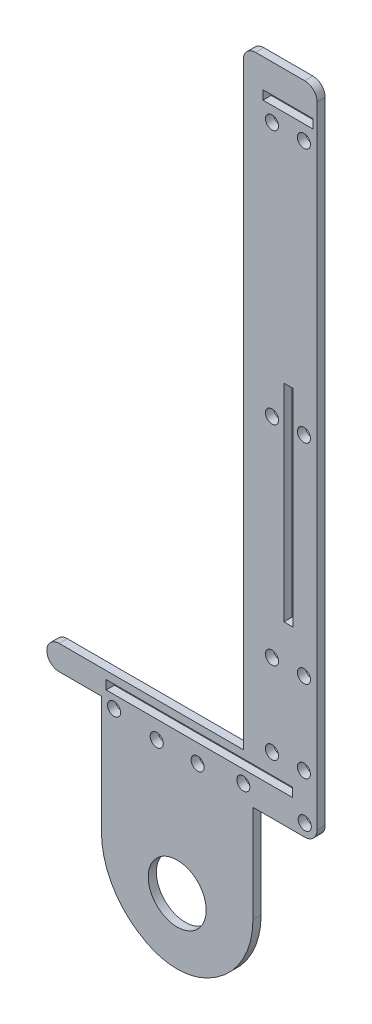
SolidWorks part; units mm, degrees
ref_plane "前视基准面" through (0, 0, 0) normal (0, 0, 1) x (1, 0, 0)
ref_plane "上视基准面" through (0, 0, 0) normal (0, 1, 0) x (1, 0, 0)
ref_plane "右视基准面" through (0, 0, 0) normal (1, 0, 0) x (0, 0, -1)
sketch "草图1" plane through (0, 0, 0) normal (0, 0, 1) x (1, 0, 0)
  line L0 (-45.6533, -106) -> (-45.6533, -80.5)
  line L1 (-11, -74.5) -> (11, -74.5)
  line L2 (-11, -74.5) -> (-11, 74.5)
  line L3 (-11, 74.5) -> (11, 74.5)
  line L4 (11, -74.5) -> (11, 74.5)
  line L5 (-11, -74.5) -> (11, 74.5) construction
  line L6 (-11, 74.5) -> (11, -74.5) construction
  line L7 (11, -74.5) -> (-59, -74.5)
  line L8 (11, -74.5) -> (11, -80.5)
  line L9 (11, -80.5) -> (-59, -80.5)
  line L10 (-59, -74.5) -> (-59, -80.5)
  line L11 (-45.6533, -106) -> (-45.6533, -109.2467)
  line L12 (-34.6655, -127.1011) -> (-27.1533, -130.893)
  line L13 (-8.6533, -106) -> (-8.6533, -80.5)
  line L14 (-8.6533, -106) -> (-8.6533, -109.2467)
  line L15 (-19.641, -127.1011) -> (-27.1533, -130.893)
  line L17 (-1.1, -42.5) -> (1.1, -42.5)
  line L18 (-1.1, -42.5) -> (-1.1, 8)
  line L19 (-1.1, 8) -> (1.1, 8)
  line L20 (1.1, -42.5) -> (1.1, 8)
  line L21 (-1.1, -42.5) -> (1.1, 8) construction
  line L22 (-1.1, 8) -> (1.1, -42.5) construction
  line L23 (-6.2, 67.5) -> (6, 67.5)
  line L24 (-6.2, 67.5) -> (-6.2, 65.3)
  line L25 (-6.2, 65.3) -> (6, 65.3)
  line L26 (6, 67.5) -> (6, 65.3)
  line L27 (-44.5, -76.4) -> (1, -76.4)
  line L28 (-44.5, -76.4) -> (-44.5, -78.6)
  line L29 (-44.5, -78.6) -> (1, -78.6)
  line L30 (1, -76.4) -> (1, -78.6)
  line L31 (-44.5, -76.4) -> (1, -78.6) construction
  line L32 (-44.5, -78.6) -> (1, -76.4) construction
  line L33 (11, -80.5) -> (-8.6533, -80.5)
  line L34 (11, -80.5) -> (11, -85.5)
  line L35 (11, -85.5) -> (-8.6533, -85.5)
  line L36 (-8.6533, -80.5) -> (-8.6533, -85.5)
  circle A0 centre (-27.1533, -113) radius 7.08
  circle A1 centre (-22.1533, -83) radius 1.6
  arc A2 (-45.6533, -106) -> (-8.6533, -106) centre (-27.1533, -106) ccw
  circle A3 centre (-32.1533, -83) radius 1.6
  circle A10 centre (-4, 61.7) radius 1.6
  circle A15 centre (-4, -0.5) radius 1.6
  circle A16 centre (3.8, -0.5) radius 1.6
  circle A17 centre (3.8, 61.7) radius 1.6
  circle A18 centre (-4, -51.5) radius 1.6
  circle A19 centre (3.8, -51.5) radius 1.6
  circle A20 centre (-4, -71.5) radius 1.6
  circle A21 centre (3.8, -71.5) radius 1.6
  circle A22 centre (-42.5707, -81.6294) radius 1.6
  circle A23 centre (-11, -81.6294) radius 1.6
  arc A24 (-45.6533, -109.2467) -> (-34.6655, -127.1011) centre (-25.6533, -109.2467) ccw
  arc A25 (-34.3511, -127.2598) -> (-19.9554, -127.2598) centre (-27.1533, -113) ccw
  arc A26 (-8.6533, -109.2467) -> (-19.641, -127.1011) centre (-28.6533, -109.2467) cw
  point P0 (0, 0)
  point P20 (0, -17.25)
  point P30 (-21.75, -77.5)
  point P52 (0, 0)
  dimension "D7" = 7
  dimension "D8" = 50.5
  dimension "D19" = 3.6
  dimension "D23" = 20
  dimension "D24" = 30
  dimension "D1" = 22
  dimension "D2" = 149
  dimension "D3" = 70
  dimension "D4" = 6
  dimension "D5" = 38.1533
  dimension "D6" = 32.5
  dimension "D9" = 2.2
  dimension "D10" = 32
  dimension "D11" = 7
  dimension "D12" = 5
  dimension "D13" = 12.2
  dimension "D14" = 2.2
  dimension "D15" = 3
  dimension "D16" = 10
  dimension "D17" = 45.5
  dimension "D18" = 2.2
  dimension "D20" = 0
  dimension "D21" = 2.2
  dimension "D22" = 2.2
  dimension "D25" = 30
  dimension "D26" = 5
  dimension "D27" = 5
  dimension "D28" = 62.2
  dimension "D29" = 51
  dimension "D30" = 0
  dimension "D31" = 20
  dimension "D32" = 0
  dimension "D33" = 0
extrude "凸台-拉伸1" add sketch "草图1" along normal blind 2 contours A21 L1 L4 L3 L2 A20 A19 A18 A17 A16 A15 A10 L20 L17 L18 L19 L23 L26 L25 L24 | A23 L9 L8 L1 A21 A20 L7 L10 A22 L27 L30 L29 L28 | A23 L9 A22 L0 A2 L13 | A0 | A2 | A26 L14 A2 L11 A24 L12 A25 L15 | L35 L34 L9 L13 region at (-27.1533, -124.9355, 0) region at (-27.1574, -99.6681, 0) region at (-52.3266, -79.7974, 0) region at (1.1734, -83, 0) region at (-9.4938, 0, 0)
sketch "草图2" plane through (0, 0, 0) normal (0, 0, -1) x (-1, 0, 0)
  line L0 (-11, -85.5) -> (8.6533, -85.5) construction
  line L1 (-11, 74.5) -> (-7, 74.5)
  line L2 (-11, 74.5) -> (-11, -85.5)
  line L3 (-11, -85.5) -> (-7, -85.5)
  line L4 (-7, 74.5) -> (-7, -85.5)
extrude "切除-拉伸1" cut sketch "草图2" against normal blind 10
sketch "草图3" plane through (0, 0, 0) normal (0, 0, -1) x (-1, 0, 0)
  line L0 (-7, -85.5) -> (8.6533, -85.5) construction
  line L1 (-7, -85.5) -> (-7, 74.5) construction
  circle A0 centre (-4, -82.5) radius 1.6
  dimension "D1" = 3
  dimension "D2" = 3
extrude "切除-拉伸2" cut sketch "草图3" against normal blind 10
fillet "圆角1" radius 3 5 edges at (-59, -74.5, 1) (-59, -80.5, 1) (7, -85.5, 1) (-11, 74.5, 1) (7, 74.5, 1)
